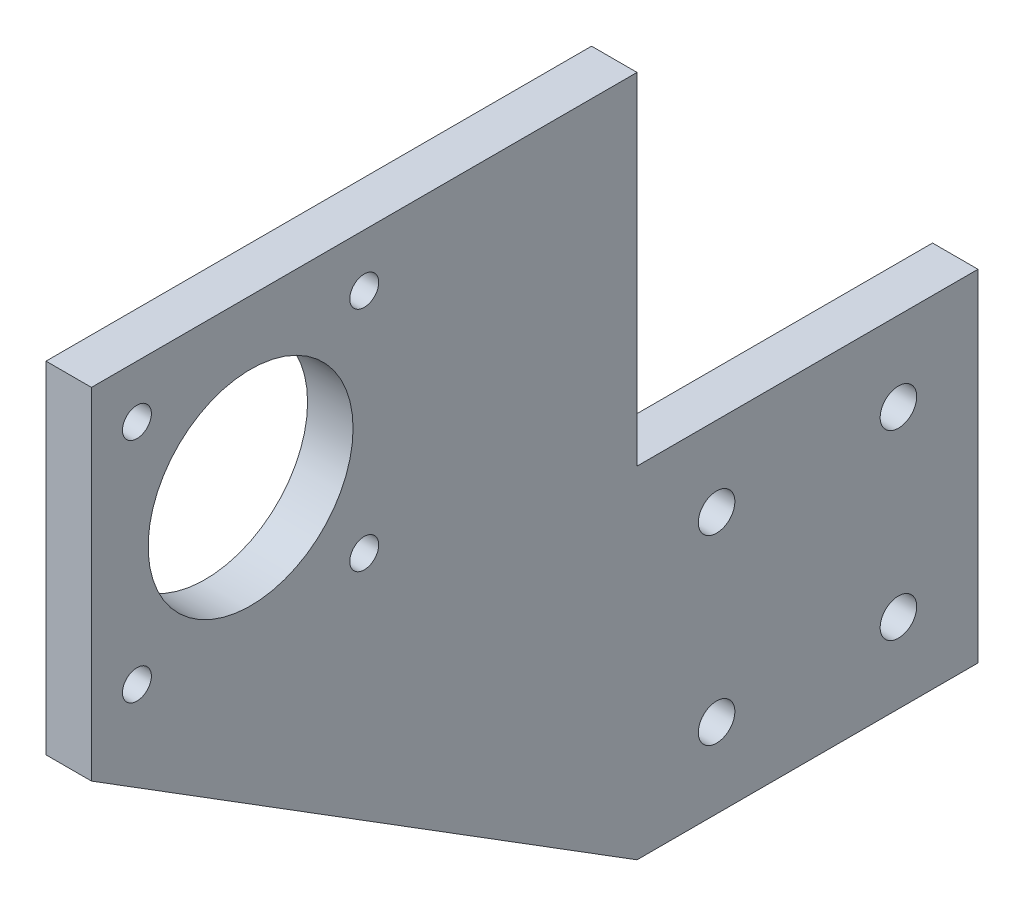
SolidWorks part; units mm, degrees
ref_plane "Front" through (0, 0, 0) normal (0, 0, 1) x (1, 0, 0)
ref_plane "Top" through (0, 0, 0) normal (0, 1, 0) x (1, 0, 0)
ref_plane "Right" through (0, 0, 0) normal (1, 0, 0) x (0, 0, -1)
sketch "Sketch1" plane through (0, 0, 0) normal (1, 0, 0) x (0, 0, -1)
  line L0 (0, 0) -> (47.625, 0)
  line L1 (47.625, 0) -> (47.625, -47.625)
  line L2 (47.625, -47.625) -> (0, -47.625)
  line L3 (0, -47.625) -> (-76.2, 0)
  line L4 (-76.2, 0) -> (-76.2, 47.625)
  line L5 (-76.2, 47.625) -> (0, 47.625)
  line L6 (0, 47.625) -> (0, 0)
  point P3 (-90.0374, 0)
  point P9 (0, 0)
  point P10 (-89.047, 0)
  point P11 (-78.5421, 0)
  point P12 (-76.2, 0)
  dimension "D1" = 47.625
  dimension "D2" = 47.625
  dimension "D3" = 76.2
extrude "Boss-Extrude1" add sketch "Sketch1" along normal blind 6.35
sketch "Sketch2" plane through (6.35, 0, 0) normal (1, 0, 0) x (0, 0, -1)
  line L1 (11.1125, -36.5125) -> (36.5125, -36.5125) construction
  line L2 (11.1125, -36.5125) -> (11.1125, -11.1125) construction
  line L3 (11.1125, -11.1125) -> (36.5125, -11.1125) construction
  line L4 (36.5125, -36.5125) -> (36.5125, -11.1125) construction
  line L5 (11.1125, -36.5125) -> (36.5125, -11.1125) construction
  line L6 (11.1125, -11.1125) -> (36.5125, -36.5125) construction
  line L7 (23.8125, 0) -> (23.8125, -23.8125) construction
  line L8 (47.625, 0) -> (0, 0) construction
  line L9 (23.8125, -23.8125) -> (47.625, -23.8125) construction
  line L10 (47.625, -47.625) -> (47.625, 0) construction
  line L11 (-53.975, 24.4) -> (-76.2, 24.4) construction
  line L12 (-76.2, 47.625) -> (-76.2, 0) construction
  line L13 (-53.975, 24.4) -> (-53.975, 47.625) construction
  line L14 (0, 47.625) -> (-76.2, 47.625) construction
  line L16 (-69.85, 8.525) -> (-38.1, 8.525) construction
  line L17 (-69.85, 8.525) -> (-69.85, 40.275) construction
  line L18 (-69.85, 40.275) -> (-38.1, 40.275) construction
  line L19 (-38.1, 8.525) -> (-38.1, 40.275) construction
  line L20 (-69.85, 8.525) -> (-38.1, 40.275) construction
  line L21 (-69.85, 40.275) -> (-38.1, 8.525) construction
  circle A0 centre (11.1125, -11.1125) radius 2.5527
  circle A1 centre (36.5125, -11.1125) radius 2.5527
  circle A2 centre (36.5125, -36.5125) radius 2.5527
  circle A3 centre (11.1125, -36.5125) radius 2.5527
  circle A4 centre (-53.975, 24.4) radius 14.3129
  circle A5 centre (-69.85, 40.275) radius 2.0193
  circle A6 centre (-38.1, 40.275) radius 2.0193
  circle A7 centre (-38.1, 8.525) radius 2.0193
  circle A8 centre (-69.85, 8.525) radius 2.0193
  point P0 (23.8125, -23.8125)
  dimension "D2" = 5.1054
  dimension "D3" = 28.6258
  dimension "D6" = 4.0386
  dimension "D1" = 25.4
  dimension "D4" = 22.225
  dimension "D5" = 6.35
  dimension "D7" = 23.225
extrude "Cut-Extrude1" cut sketch "Sketch2" against normal through all
